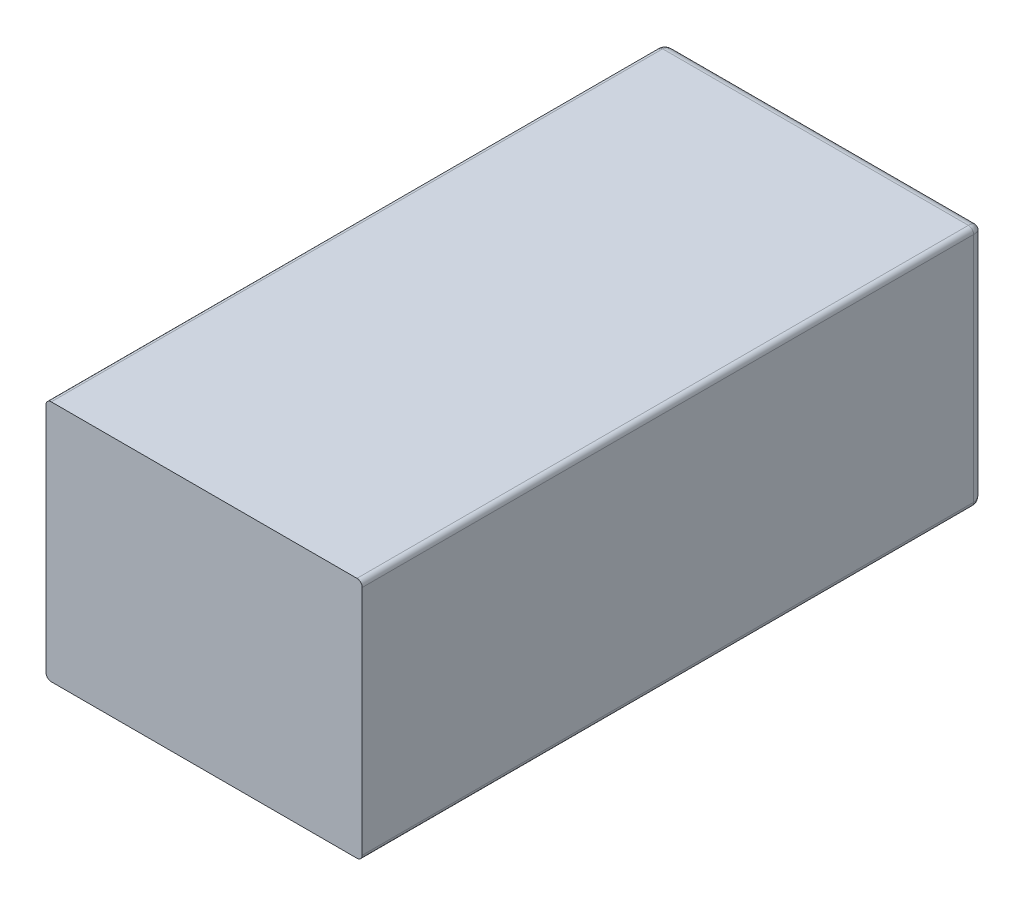
SolidWorks part; units mm, degrees
ref_plane "Front Plane" through (0, 0, 0) normal (0, 0, 1) x (1, 0, 0)
ref_plane "Top Plane" through (0, 0, 0) normal (0, 1, 0) x (1, 0, 0)
ref_plane "Right Plane" through (0, 0, 0) normal (1, 0, 0) x (0, 0, -1)
sketch "Sketch1" plane through (0, 0, 0) normal (0, 0, 1) x (1, 0, 0)
  line L5 (15, -11.5) -> (-15, -11.5)
  line L6 (15, -11.5) -> (15, 11.5)
  line L7 (15, 11.5) -> (-15, 11.5)
  line L8 (-15, -11.5) -> (-15, 11.5)
  line L9 (15, -11.5) -> (-15, 11.5) construction
  line L10 (15, 11.5) -> (-15, -11.5) construction
  point P0 (0, 0)
  dimension "D1" = 30
  dimension "D2" = 23
extrude "Boss-Extrude1" add sketch "Sketch1" along normal mid plane 59
fillet "Fillet1" radius 0.5 4 edges at (-15, -11.5, 0) (15, -11.5, 0) (-15, 11.5, 0) (15, 11.5, 0)
fillet "Fillet2" radius 1 8 edges at (14.8536, 11.3536, -29.5) (15, 0, -29.5) (14.8536, -11.3536, -29.5) (0, -11.5, -29.5) (-14.8536, -11.3536, -29.5) (-15, 0, -29.5) (-14.8536, 11.3536, -29.5) (0, 11.5, -29.5)
